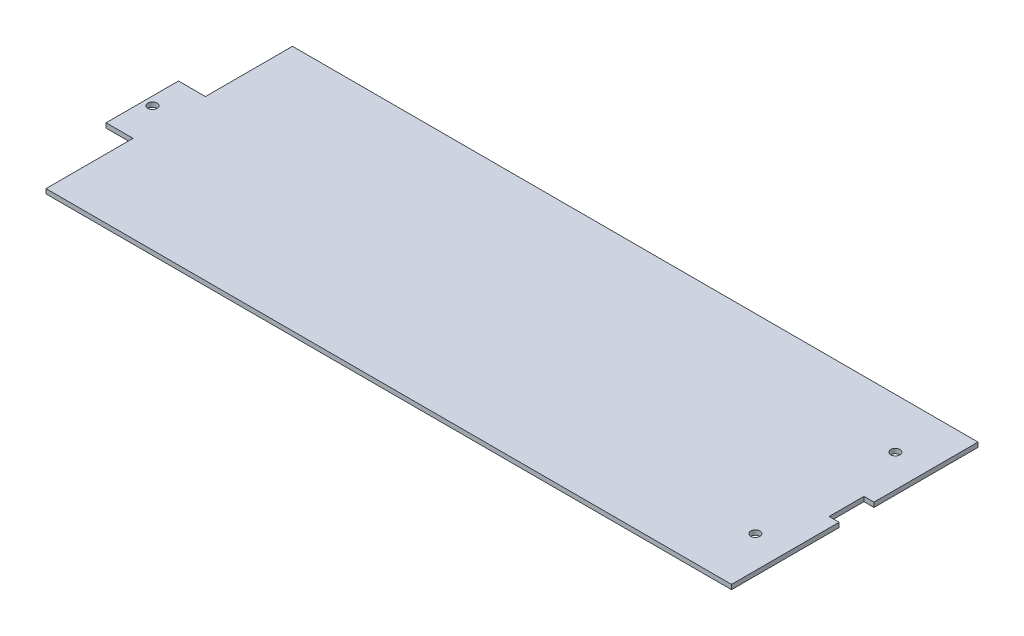
SolidWorks part; units mm, degrees
ref_plane "Front Plane" through (0, 0, 0) normal (0, 0, 1) x (1, 0, 0)
ref_plane "Top Plane" through (0, 0, 0) normal (0, 1, 0) x (1, 0, 0)
ref_plane "Right Plane" through (0, 0, 0) normal (1, 0, 0) x (0, 0, -1)
sketch "Sketch1" plane through (0, 0, 0) normal (0, 1, 0) x (1, 0, 0)
  line L0 (-302.2355, -755.753) -> (-284.7355, -755.753)
  line L1 (-284.7355, -699.253) -> (160.2645, -699.253)
  line L2 (-284.7355, -699.253) -> (-284.7355, -755.753)
  line L5 (-296.7465, -853.0209) -> (-296.7465, -703.1609) construction
  line L6 (-284.7355, -699.253) -> (-286.6881, -713.2193) construction
  line L7 (-302.2355, -755.753) -> (-302.2355, -802.753)
  line L8 (-302.2355, -802.753) -> (-284.7355, -802.753)
  line L9 (-284.7355, -802.753) -> (-284.7355, -859.253)
  line L10 (-284.7355, 31.0446) -> (-284.7355, -755.753) construction
  line L11 (160.2645, -699.253) -> (160.2645, -766.7909)
  line L12 (160.2645, -766.7909) -> (153.7645, -766.7909)
  line L13 (-302.2355, -779.253) -> (-26.2365, -778.0909) construction
  line L14 (161.6735, -769.7909) -> (169.6735, -769.7909) construction
  line L15 (153.7645, -766.7909) -> (153.7645, -789.3909)
  line L16 (153.7645, -789.3909) -> (160.2645, -789.3909)
  line L17 (169.6735, -786.3909) -> (161.6735, -786.3909) construction
  line L18 (160.2645, -789.3909) -> (160.2645, -859.253)
  line L19 (160.2645, -859.253) -> (-284.7355, -859.253)
  line L20 (-194.7355, 72.7736) -> (70.2645, 72.7736) construction
  circle A0 centre (-296.7465, -778.0909) radius 3
  circle A1 centre (-194.7355, 72.7736) radius 3
  circle A2 centre (70.2645, 72.7736) radius 3.5
  circle A3 centre (77.426, -1628.1126) radius 3.5
  circle A4 centre (-187.5646, -1630.3441) radius 3
  circle A5 centre (139.1024, -731.753) radius 3
  circle A6 centre (139.4867, -823.0348) radius 3
  point P4 (0, 0)
  dimension "D9" = 6.5
  dimension "D12" = 6
  dimension "D3" = 6
  dimension "D15" = 6
  dimension "D16" = 7
  dimension "D1" = 56.5
  dimension "D2" = 56.5
  dimension "D4" = 3
  dimension "D5" = 3
  dimension "D6" = 17.5
  dimension "D7" = 445
  dimension "D8" = 69.8621
  dimension "D10" = 160
  dimension "D11" = 67.5379
  dimension "D13" = 90
  dimension "D14" = 90
  dimension "D17" = 32.5
extrude "Boss-Extrude1" add sketch "Sketch1" along normal blind 3 from offset 2 contours L8 L9 L1 L2 L0 L7 region at (-65.4, 0, 779.2573)
